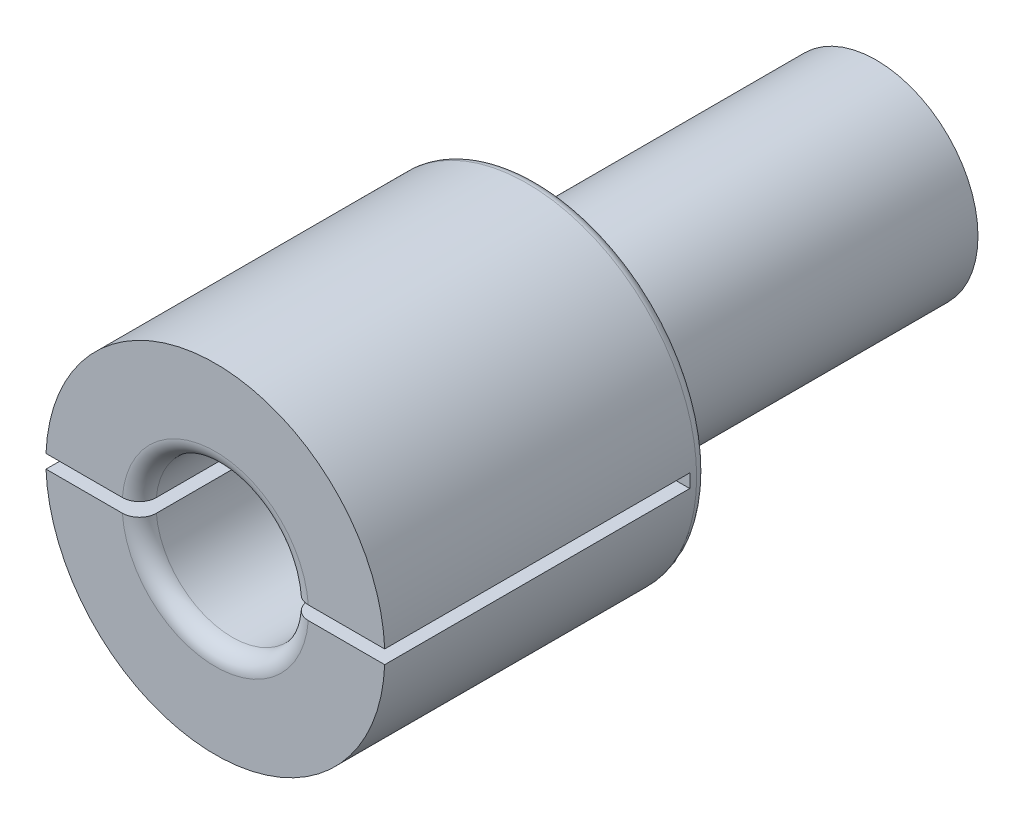
SolidWorks part; units mm, degrees
material "Cobre forjado"
ref_plane "Plano frontal" through (0, 0, 0) normal (0, 0, 1) x (1, 0, 0)
ref_plane "Plano superior" through (0, 0, 0) normal (0, 1, 0) x (1, 0, 0)
ref_plane "Plano direito" through (0, 0, 0) normal (1, 0, 0) x (0, 0, -1)
sketch "Esboço1" plane through (0, 0, 0) normal (0, 0, 1) x (1, 0, 0)
  circle A0 centre (-26.1833, 4.3838) radius 5
  dimension "D1" = 10
extrude "Ressalto-extrusão1" add sketch "Esboço1" along normal blind 9.5
sketch "Esboço2" plane through (0, 0, 9.5) normal (0, 0, 1) x (1, 0, 0)
  circle A0 centre (-26.1833, 4.3838) radius 2.25
  dimension "D1" = 4.5
extrude "Corte-extrusão1" cut sketch "Esboço2" against normal blind 11
sketch "Esboço3" plane through (0, 0, 0) normal (0, 0, -1) x (-1, 0, 0)
  circle A0 centre (26.1833, 4.3838) radius 3
  dimension "D1" = 6
extrude "Ressalto-extrusão2" add sketch "Esboço3" along normal blind 10
cosmetic thread "Representação de rosca1" parameters "D2"=4.891
sketch "Esboço4" plane through (0, 0, 9.5) normal (0, 0, 1) x (1, 0, 0)
  line L0 (-26.1833, 4.3838) -> (49973.8167, 4.3838) construction
  line L1 (-31.1833, 4.3838) -> (-21.1833, 4.3838) construction
  line L2 (-31.1833, 4.5838) -> (-21.1833, 4.5838)
  line L3 (-31.1833, 4.1838) -> (-21.1833, 4.1838)
  circle A0 centre (-26.1833, 4.3838) radius 5 construction
  arc A1 (-31.1833, 4.5838) -> (-31.1833, 4.1838) centre (-31.1833, 4.3838) ccw
  arc A2 (-21.1833, 4.1838) -> (-21.1833, 4.5838) centre (-21.1833, 4.3838) ccw
  point P7 (-26.1833, 4.3838)
  dimension "D1" = 0.4
extrude "Corte-extrusão2" cut sketch "Esboço4" against normal blind 9
fillet "Filete1" radius 0.5 2 edges at (-26.1833, 2.1338, 9.5) (-26.1833, 6.6338, 9.5)
fillet "Filete2" radius 0.3 1 edges at (-21.1833, 4.3838, 0)
chamfer "Chanfro1" distance 1 angle 45 1 edges at (-23.9333, 4.3838, 0)
